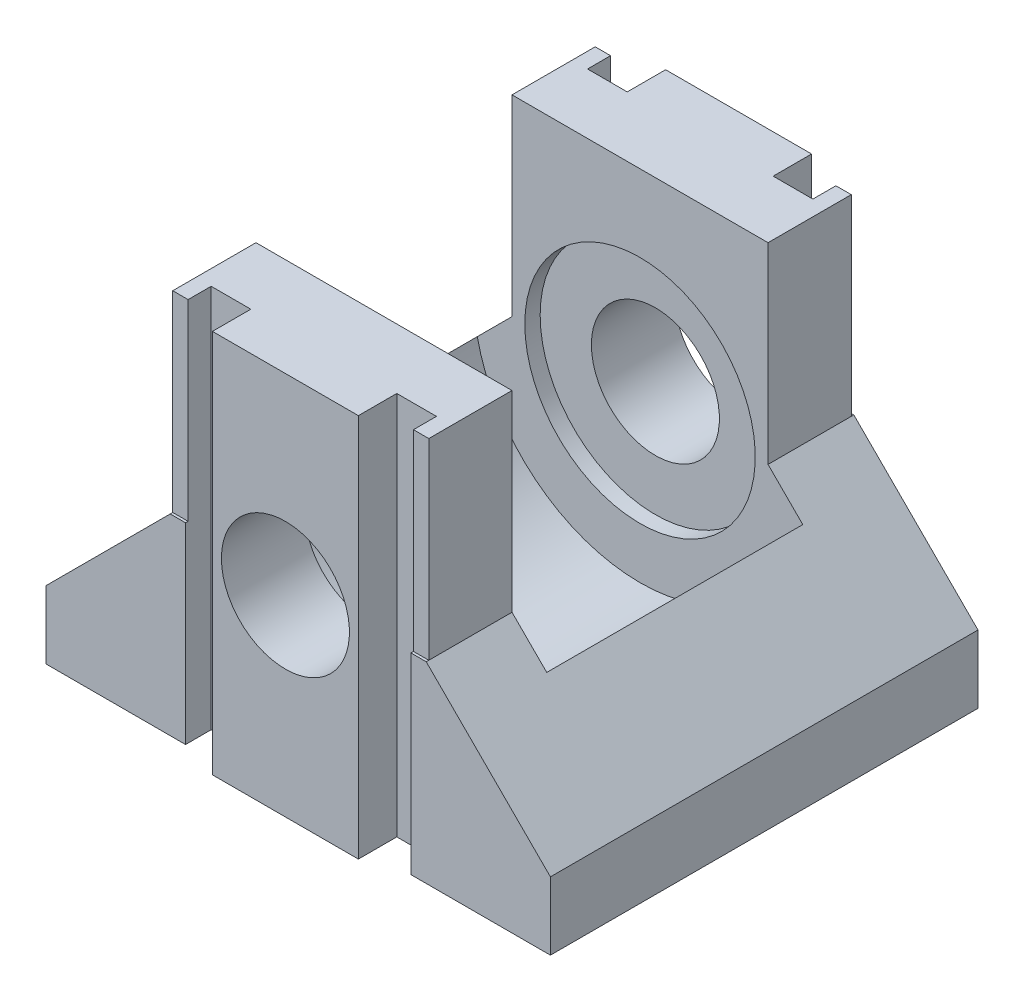
SolidWorks part; units mm, degrees
ref_plane "Płaszczyzna przednia" through (0, 0, 0) normal (0, 0, 1) x (1, 0, 0)
ref_plane "Płaszczyzna górna" through (0, 0, 0) normal (0, 1, 0) x (1, 0, 0)
ref_plane "Płaszczyzna prawa" through (0, 0, 0) normal (1, 0, 0) x (0, 0, -1)
sketch "Sketch5" plane through (0, 0, 0) normal (0, 0, 1) x (1, 0, 0)
  line L1 (-40, 15) -> (0, 15)
  line L2 (-40, 15) -> (-40, 0)
  line L3 (-40, 0) -> (0, 0)
  line L4 (0, 15) -> (0, 0)
  dimension "D1" = 40
  dimension "D2" = 15
extrude "Boss-Extrude2" add sketch "Sketch5" along normal blind 17
sketch "Sketch6" plane through (0, 0, 0) normal (0, 0, -1) x (-1, 0, 0)
  line L0 (0, 15) -> (40, 15) construction
  circle A0 centre (20, 15) radius 13
  dimension "D1" = 26
extrude "Cut-Extrude4" cut sketch "Sketch6" against normal blind 10
sketch "Sketch7" plane through (0, 0, 17) normal (0, 0, 1) x (1, 0, 0)
  line L0 (0, 15) -> (-40, 15) construction
  circle A0 centre (-20, 15) radius 2.5
  dimension "D1" = 5
extrude "Cut-Extrude5" cut sketch "Sketch7" against normal blind 4.5 contours A0
mirror "Mirror5" about plane through (0, 0, 0) normal (0, 0, 1) of "Cut-Extrude4", "Cut-Extrude5", "Boss-Extrude2"
sketch "Sketch8" plane through (0, 0, 0) normal (0, -1, 0) x (1, 0, 0)
  line L0 (-40, 0) -> (0, 0) construction
  line L1 (-20, 17) -> (-20, -17) construction
  line L2 (-40, 17) -> (-40, -17) construction
  line L3 (0, 17) -> (0, -17) construction
  line L4 (-40, -17) -> (0, -17) construction
  line L5 (-40, 17) -> (0, 17) construction
  circle A0 centre (-33, 11.5) radius 4.8
  circle A1 centre (-7, 11.5) radius 4.8
  circle A2 centre (-7, -11.5) radius 4.8
  circle A3 centre (-33, -11.5) radius 4.8
  dimension "D1" = 9.6
  dimension "D2" = 5.5
  dimension "D3" = 7
chamfer "Chamfer8" distance 10 angle 45 2 edges at (-40, 15, 0) (0, 15, 0)
sketch "Sketch10" plane through (0, 0, -10) normal (0, 0, 1) x (1, 0, 0)
  line L0 (-30, 15) -> (-22.5, 15)
  line L1 (-17.5, 15) -> (-10, 15)
  line L2 (-30, 30) -> (-10, 30)
  line L3 (-30, 30) -> (-30, 15)
  line L4 (-30, 15) -> (-22.5, 15)
  line L5 (-10, 30) -> (-10, 15)
  line L6 (-17.5, 15) -> (-10, 15)
  circle A0 centre (-20, 15) radius 2.5
  arc A1 (-30, 15) -> (-10, 15) centre (-20, 15) ccw
  arc A2 (-22.5, 15) -> (-17.5, 15) centre (-20, 15) ccw construction
  circle A3 centre (-20, 15) radius 10 construction
  line M3 (-10, 15) -> (-30, 15)
  line M7 (-10, 15) -> (-30, 15)
  dimension "D1" = 15
extrude "Boss-Extrude3" add sketch "Sketch10" against normal blind 6.5 contours A0 L5 L2 L3 M7 M3 | A0 region at (-20, 22.7178, -10)
ref_plane "Plane1" through (0, 0, 0) normal (0, 0, -1) x (-1, 0, 0)
mirror "Mirror6" about plane through (0, 0, 0) normal (0, 0, -1) of "Boss-Extrude3"
extrude "Cut-Extrude8" cut sketch "Sketch8" against normal blind 3
sketch "Sketch9" plane through (0, 0, 0) normal (0, -1, 0) x (1, 0, 0)
  line L0 (-20, 17) -> (-20, -17) construction
  line L1 (-40, 0) -> (0, 0) construction
  line L3 (-40, 17) -> (0, 17) construction
  line L4 (-40, 17) -> (-40, -17) construction
  line L5 (-40, -17) -> (0, -17) construction
  line L6 (0, 17) -> (0, -17) construction
  line L7 (-11.5, 15) -> (-14, 15)
  line L8 (-28.5, 17) -> (-26, 17)
  line L9 (-28.5, 17) -> (-28.5, 15)
  line L10 (-28.5, 15) -> (-26, 15)
  line L11 (-26, 17) -> (-26, 15)
  line L12 (-14, 17) -> (-14, 15)
  line L13 (-11.5, 17) -> (-14, 17)
  line L14 (-11.5, 17) -> (-11.5, 15)
  line L15 (-11.5, -17) -> (-11.5, -15)
  line L16 (-11.5, -17) -> (-14, -17)
  line L17 (-14, -17) -> (-14, -15)
  line L18 (-11.5, -15) -> (-14, -15)
  line L19 (-28.5, -15) -> (-26, -15)
  line L20 (-26, -17) -> (-26, -15)
  line L21 (-28.5, -17) -> (-26, -17)
  line L22 (-28.5, -17) -> (-28.5, -15)
  dimension "D1" = 2.5
  dimension "D2" = 2
  dimension "D3" = 6
extrude "Cut-Extrude7" cut sketch "Sketch9" against normal blind 52
sketch "Sketch11" plane through (0, 0, 10) normal (0, 0, -1) x (-1, 0, 0)
  circle A0 centre (20, 15) radius 5
  arc A1 (7.2864, 12.2864) -> (32.7136, 12.2864) centre (20, 15) ccw construction
  dimension "D1" = 10
extrude "Cut-Extrude9" cut sketch "Sketch11" against normal mid plane 90
sketch "Sketch12" plane through (0, 0, 10) normal (0, 0, -1) x (-1, 0, 0)
  circle A0 centre (20, 15) radius 5
  circle A1 centre (20, 15) radius 5 construction
  circle A2 centre (20, 15) radius 9
  dimension "D1" = 18
extrude "Cut-Extrude11" cut sketch "Sketch12" against normal blind 1.2
mirror "Mirror7" about plane through (0, 0, 0) normal (0, 0, -1) of "Cut-Extrude11"
sketch "Sketch13" plane through (0, 0, 0) normal (0, -1, 0) x (1, 0, 0)
  line L20 (-25.7, 14.7) -> (-28.8, 14.7)
  line L26 (-28.8, 14.7) -> (-28.8, 16.7)
  line L27 (-28.8, 16.7) -> (-39.7, 16.7)
  line L30 (-39.7, 16.7) -> (-39.7, -16.7)
  line L31 (-39.7, -16.7) -> (-28.8, -16.7)
  line L36 (-28.8, -16.7) -> (-28.8, -14.7)
  line L37 (-28.8, -14.7) -> (-25.7, -14.7)
  line L60 (-25.7, -14.7) -> (-25.7, -16.7)
  line L61 (-25.7, -16.7) -> (-14.3, -16.7)
  line L62 (-14.3, -16.7) -> (-14.3, -14.7)
  line L63 (-14.3, -14.7) -> (-11.2, -14.7)
  line L64 (-11.2, -14.7) -> (-11.2, -16.7)
  line L65 (-11.2, -16.7) -> (-0.3, -16.7)
  line L66 (-0.3, -16.7) -> (-0.3, 16.7)
  line L67 (-0.3, 16.7) -> (-11.2, 16.7)
  line L68 (-11.2, 16.7) -> (-11.2, 14.7)
  line L69 (-11.2, 14.7) -> (-14.3, 14.7)
  line L70 (-14.3, 14.7) -> (-14.3, 16.7)
  line L71 (-14.3, 16.7) -> (-25.7, 16.7)
  line L72 (-25.7, 16.7) -> (-25.7, 14.7)
  line L73 (-26, 15) -> (-28.5, 15)
  line L74 (-28.5, 15) -> (-28.5, 17)
  line L75 (-28.5, 17) -> (-40, 17)
  line L76 (-40, 17) -> (-40, -17)
  line L77 (-40, -17) -> (-28.5, -17)
  line L78 (-28.5, -17) -> (-28.5, -15)
  line L79 (-28.5, -15) -> (-26, -15)
  line L80 (-26, -15) -> (-26, -17)
  line L81 (-26, -17) -> (-14, -17)
  line L84 (-14, -17) -> (-14, -15)
  line L85 (-14, -15) -> (-11.5, -15)
  line L86 (-11.5, -15) -> (-11.5, -17)
  line L87 (-11.5, -17) -> (0, -17)
  line L88 (0, -17) -> (0, 17)
  line L89 (0, 17) -> (-11.5, 17)
  line L90 (-11.5, 17) -> (-11.5, 15)
  line L91 (-11.5, 15) -> (-14, 15)
  line L92 (-14, 15) -> (-14, 17)
  line L93 (-14, 17) -> (-26, 17)
  line L94 (-26, 17) -> (-26, 15)
  line L95 (-26, 15) -> (-28.5, 15)
  line L96 (-28.5, 15) -> (-28.5, 17)
  line L97 (-28.5, 17) -> (-40, 17)
  line L98 (-40, 17) -> (-40, -17)
  line L99 (-40, -17) -> (-28.5, -17)
  line L100 (-28.5, -17) -> (-28.5, -15)
  line L101 (-28.5, -15) -> (-26, -15)
  line L102 (-26, -15) -> (-26, -17)
  line L103 (-26, -17) -> (-14, -17)
  line L104 (-14, -17) -> (-14, -15)
  line L105 (-14, -15) -> (-11.5, -15)
  line L106 (-11.5, -15) -> (-11.5, -17)
  line L107 (-11.5, -17) -> (0, -17)
  line L108 (0, -17) -> (0, 17)
  line L109 (0, 17) -> (-11.5, 17)
  line L110 (-11.5, 17) -> (-11.5, 15)
  line L111 (-11.5, 15) -> (-14, 15)
  line L112 (-14, 15) -> (-14, 17)
  line L113 (-14, 17) -> (-26, 17)
  line L114 (-26, 17) -> (-26, 15)
  dimension "D1" = 0
  dimension "D2" = 0.3
extrude "Cut-Extrude12" cut sketch "Sketch13" against normal through all
sketch "Sketch14" plane through (0, 0, -16.7) normal (0, 0, -1) x (-1, 0, 0)
  line L15 (15, 15) -> (14.3, 15)
  line L16 (14.3, 15) -> (14.3, 0)
  line L17 (14.3, 0) -> (25.7, 0)
  line L18 (25.7, 0) -> (25.7, 15)
  line L19 (25.7, 15) -> (25, 15)
  line L20 (15, 15) -> (14.3, 15)
  line L21 (14.3, 15) -> (14.3, 0)
  line L22 (14.3, 0) -> (25.7, 0)
  line L23 (25.7, 0) -> (25.7, 15)
  line L24 (25.7, 15) -> (25, 15)
  arc A3 (15, 15) -> (25, 15) centre (20, 15) ccw
  arc A4 (15, 15) -> (25, 15) centre (20, 15) ccw
  dimension "D1" = 0
extrude "Boss-Extrude4" add sketch "Sketch14" along normal blind 1
extrude "Boss-Extrude8" add sketch "Sketch14<3>" against normal blind 1 from surface starting at face at (-20, 9.1667, 16.7)
sketch "Sketch14<3>" plane through (0, 0, -16.7) normal (0, 0, -1) x (-1, 0, 0) same geometry as "Sketch14"
sketch "Sketch16" plane through (0, 0, 16.5) normal (0, 0, 1) x (1, 0, 0)
  line L5 (-25.7, 30) -> (-25.7, 15)
  line L6 (-25.7, 15) -> (-25, 15)
  line L7 (-15, 15) -> (-14.3, 15)
  line L8 (-14.3, 15) -> (-14.3, 30)
  line L9 (-14.3, 30) -> (-25.7, 30)
  line L10 (-25.7, 30) -> (-25.7, 15)
  line L11 (-25.7, 15) -> (-25, 15)
  line L12 (-15, 15) -> (-14.3, 15)
  line L13 (-14.3, 15) -> (-14.3, 30)
  line L14 (-14.3, 30) -> (-25.7, 30)
  arc A1 (-15, 15) -> (-25, 15) centre (-20, 15) ccw
  arc A2 (-15, 15) -> (-25, 15) centre (-20, 15) ccw
  dimension "D1" = 0
extrude "Boss-Extrude9" add sketch "Sketch16" along normal up to surface (1.2 mm away) up to face at (-20, 9.1667, 17.7)
extrude "Boss-Extrude10" add sketch "Sketch16<2>" against normal up to surface (34.2 mm away) from surface up to face at (-20, 9.1667, -17.7) starting at face at (-20, 20.8333, -16.5)
sketch "Sketch16<2>" plane through (0, 0, 16.5) normal (0, 0, 1) x (1, 0, 0) same geometry as "Sketch16"
